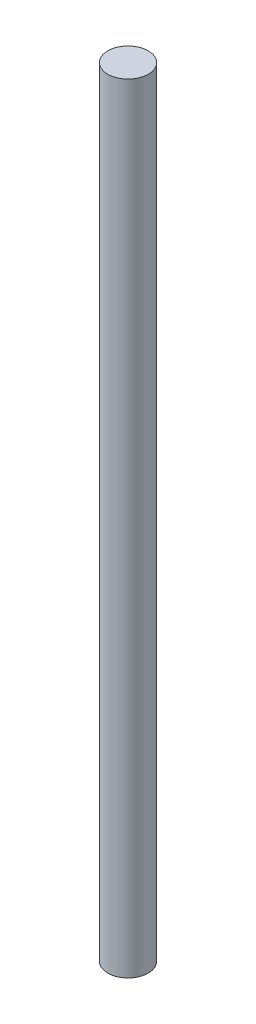
SolidWorks part; units mm, degrees
ref_plane "Front Plane" through (0, 0, 0) normal (0, 0, 1) x (1, 0, 0)
ref_plane "Top Plane" through (0, 0, 0) normal (0, 1, 0) x (1, 0, 0)
ref_plane "Right Plane" through (0, 0, 0) normal (1, 0, 0) x (0, 0, -1)
sketch "Sketch1" plane through (0, 0, 0) normal (0, 1, 0) x (1, 0, 0)
  circle A0 centre (0, 0) radius 7.9375
  dimension "D1" = 15.875
extrude "Boss-Extrude1" add sketch "Sketch1" along normal mid plane 304.8
